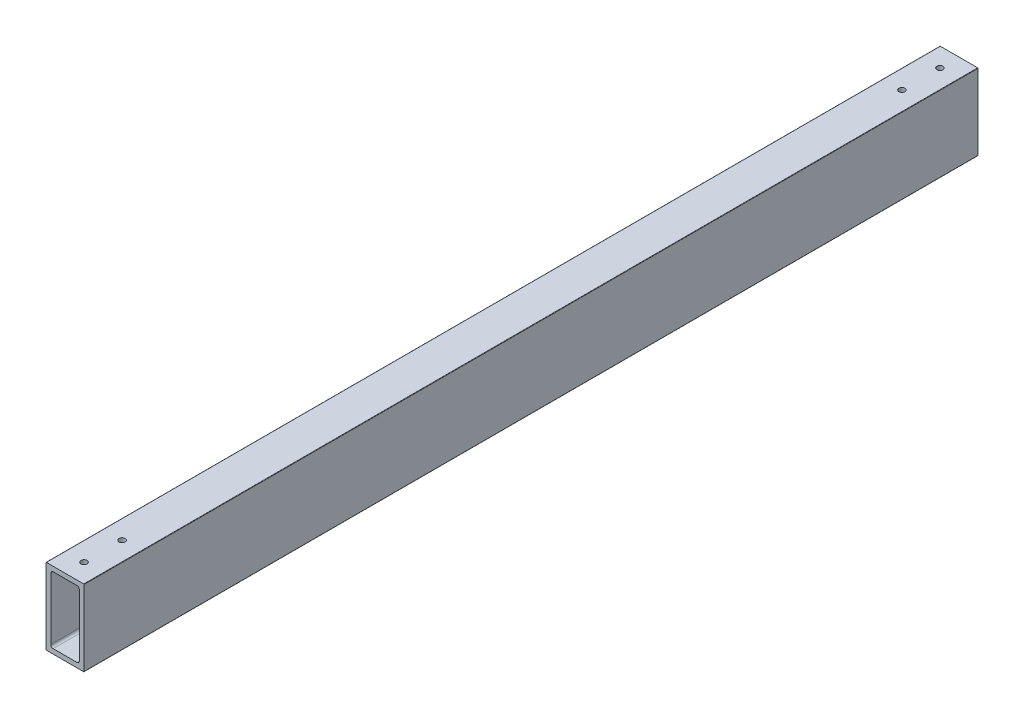
SolidWorks part; units mm, degrees
material "3.0205 (EN-AW 1200)"
ref_plane "Front Plane" through (0, 0, 0) normal (0, 0, 1) x (1, 0, 0)
ref_plane "Top Plane" through (0, 0, 0) normal (0, 1, 0) x (1, 0, 0)
ref_plane "Right Plane" through (0, 0, 0) normal (1, 0, 0) x (0, 0, -1)
ref_plane "Plane1" through (0, 0, 0) normal (0, 0, -1) x (-1, 0, 0)
sketch "Sketch1" plane through (0, 0, 0) normal (0, 0, -1) x (-1, 0, 0)
  line L0 (-3.175, 46.0375) -> (-3.175, 4.7625)
  line L1 (-4.7625, 3.175) -> (-20.6375, 3.175)
  line L2 (-22.225, 4.7625) -> (-22.225, 46.0375)
  line L3 (-20.6375, 47.625) -> (-4.7625, 47.625)
  line L4 (0, 0.254) -> (0, 50.546)
  line L5 (-0.254, 50.8) -> (-25.146, 50.8)
  line L6 (-25.4, 50.546) -> (-25.4, 0.254)
  line L7 (-25.146, 0) -> (-0.254, 0)
  arc A0 (-3.175, 4.7625) -> (-4.7625, 3.175) centre (-4.7625, 4.7625) cw
  arc A1 (-20.6375, 3.175) -> (-22.225, 4.7625) centre (-20.6375, 4.7625) cw
  arc A2 (-22.225, 46.0375) -> (-20.6375, 47.625) centre (-20.6375, 46.0375) cw
  arc A3 (-4.7625, 47.625) -> (-3.175, 46.0375) centre (-4.7625, 46.0375) cw
  arc A4 (-0.254, 0) -> (0, 0.254) centre (-0.254, 0.254) ccw
  arc A5 (0, 50.546) -> (-0.254, 50.8) centre (-0.254, 50.546) ccw
  arc A6 (-25.146, 50.8) -> (-25.4, 50.546) centre (-25.146, 50.546) ccw
  arc A7 (-25.4, 0.254) -> (-25.146, 0) centre (-25.146, 0.254) ccw
extrude "Boss-Extrude1" add sketch "Sketch1" against normal blind 596.9
sketch "Sketch2" plane through (0, 50.8, 0) normal (0, 1, 0) x (1, 0, 0)
  line L0 (0.254, -596.9) -> (25.146, -596.9) construction
  line L1 (25.146, -298.45) -> (0, -298.45) construction
  line L2 (25.146, -596.9) -> (25.146, 0) construction
  line L3 (0, -596.9) -> (0, 0) construction
  circle A0 centre (12.7, -584.2) radius 2.032
  circle A1 centre (12.7, -558.8) radius 2.032
  circle A2 centre (12.7, -38.1) radius 2.032
  circle A3 centre (12.7, -12.7) radius 2.032
  dimension "D1" = 4.064
  dimension "D2" = 4.064
  dimension "D3" = 12.7
  dimension "D4" = 25.4
extrude "Cut-Extrude1" cut sketch "Sketch2" against normal through all
